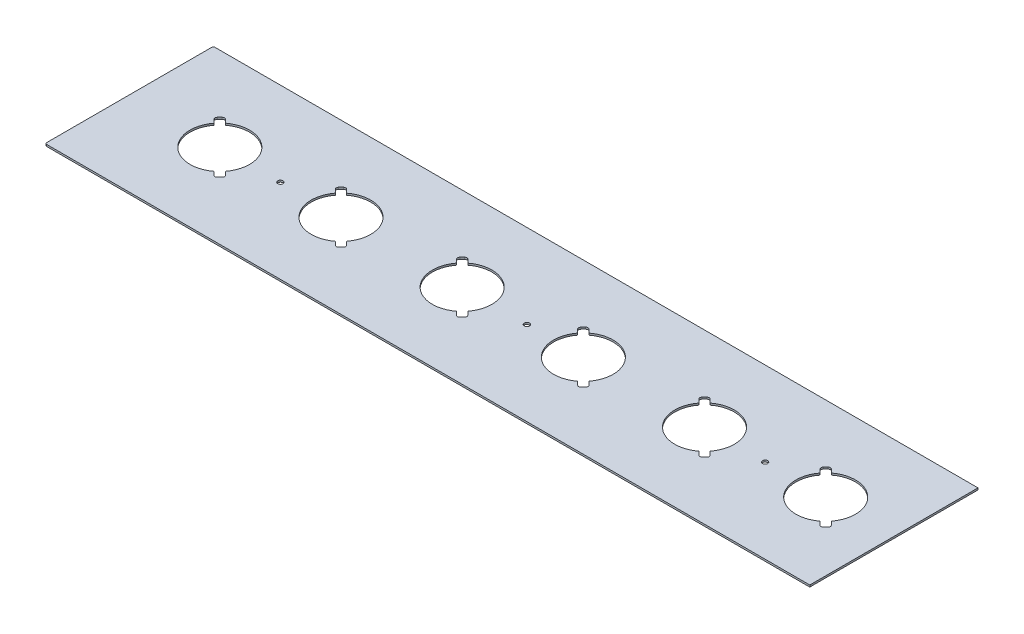
SolidWorks part; units mm, degrees
material "E-Glass Fiber"
ref_plane "Front" through (0, 0, 0) normal (0, 0, 1) x (1, 0, 0)
ref_plane "Top" through (0, 0, 0) normal (0, 1, 0) x (1, 0, 0)
ref_plane "Right" through (0, 0, 0) normal (1, 0, 0) x (0, 0, -1)
sketch "Sketch2" plane through (0, 0, 0) normal (0, 1, 0) x (1, 0, 0)
  line L1 (-317.5, 69.85) -> (317.5, 69.85)
  line L2 (-317.5, 69.85) -> (-317.5, -69.85)
  line L3 (-317.5, -69.85) -> (317.5, -69.85)
  line L5 (317.5, 69.85) -> (317.5, -69.85)
  line L6 (-317.5, 69.85) -> (317.5, -69.85) construction
  line L13 (180.1482, -15.1494) -> (182.7999, -17.8011) construction
  line L14 (182.7999, -20.6295) -> (180.8907, -22.5387) construction
  line L18 (178.0623, -22.5387) -> (175.4106, -19.887) construction
  line L19 (142.4601, 22.5387) -> (145.1118, 19.887) construction
  line L20 (140.3742, 15.1494) -> (137.7225, 17.8011) construction
  line L24 (137.7225, 20.6295) -> (139.6317, 22.5387) construction
  line L25 (179.9443, -14.9455) -> (182.7999, -17.8011)
  line L30 (182.7999, -20.6295) -> (180.8907, -22.5387)
  line L31 (178.0623, -22.5387) -> (175.2067, -19.6831)
  line L32 (142.4601, 22.5387) -> (145.3157, 19.6831)
  line L36 (140.5781, 14.9455) -> (137.7225, 17.8011)
  line L37 (137.7225, 20.6295) -> (139.6317, 22.5387)
  line L38 (39.7394, 15.1494) -> (37.0877, 17.8011) construction
  line L42 (243.0949, 22.5387) -> (245.7466, 19.887) construction
  line L43 (238.3573, 20.6295) -> (240.2665, 22.5387) construction
  line L44 (241.009, 15.1494) -> (238.3573, 17.8011) construction
  line L45 (243.0949, 22.5387) -> (245.9505, 19.6831)
  line L46 (238.3573, 20.6295) -> (240.2665, 22.5387)
  line L47 (241.2129, 14.9455) -> (238.3573, 17.8011)
  line L48 (280.783, -15.1494) -> (283.4347, -17.8011) construction
  line L49 (283.4347, -20.6295) -> (281.5255, -22.5387) construction
  line L50 (278.6971, -22.5387) -> (276.0454, -19.887) construction
  line L51 (280.5791, -14.9455) -> (283.4347, -17.8011)
  line L52 (283.4347, -20.6295) -> (281.5255, -22.5387)
  line L53 (278.6971, -22.5387) -> (275.8415, -19.6831)
  line L78 (37.0877, 20.6295) -> (38.9969, 22.5387) construction
  line L79 (41.8253, 22.5387) -> (44.477, 19.887) construction
  line L80 (79.5134, -15.1494) -> (82.1651, -17.8011) construction
  line L81 (82.1651, -20.6295) -> (80.2559, -22.5387) construction
  line L82 (77.4275, -22.5387) -> (74.7758, -19.887) construction
  line L83 (39.9433, 14.9455) -> (37.0877, 17.8011)
  line L84 (37.0877, 20.6295) -> (38.9969, 22.5387)
  line L85 (41.8253, 22.5387) -> (44.6809, 19.6831)
  line L86 (79.3095, -14.9455) -> (82.1651, -17.8011)
  line L87 (82.1651, -20.6295) -> (80.2559, -22.5387)
  line L88 (77.4275, -22.5387) -> (74.5719, -19.6831)
  line L89 (-60.8954, 15.1494) -> (-63.5471, 17.8011) construction
  line L90 (-63.5471, 20.6295) -> (-61.6379, 22.5387) construction
  line L91 (-58.8095, 22.5387) -> (-56.1578, 19.887) construction
  line L92 (-21.1214, -15.1494) -> (-18.4697, -17.8011) construction
  line L93 (-18.4697, -20.6295) -> (-20.3789, -22.5387) construction
  line L94 (-23.2073, -22.5387) -> (-25.859, -19.887) construction
  line L95 (-60.6915, 14.9455) -> (-63.5471, 17.8011)
  line L96 (-63.5471, 20.6295) -> (-61.6379, 22.5387)
  line L97 (-58.8095, 22.5387) -> (-55.9539, 19.6831)
  line L98 (-21.3253, -14.9455) -> (-18.4697, -17.8011)
  line L99 (-18.4697, -20.6295) -> (-20.3789, -22.5387)
  line L100 (-23.2073, -22.5387) -> (-26.0629, -19.6831)
  line L101 (-161.5302, 15.1494) -> (-164.1819, 17.8011) construction
  line L102 (-164.1819, 20.6295) -> (-162.2727, 22.5387) construction
  line L103 (-159.4443, 22.5387) -> (-156.7926, 19.887) construction
  line L104 (-121.7562, -15.1494) -> (-119.1045, -17.8011) construction
  line L105 (-119.1045, -20.6295) -> (-121.0137, -22.5387) construction
  line L106 (-123.8421, -22.5387) -> (-126.4938, -19.887) construction
  line L107 (-161.3263, 14.9455) -> (-164.1819, 17.8011)
  line L108 (-164.1819, 20.6295) -> (-162.2727, 22.5387)
  line L109 (-159.4443, 22.5387) -> (-156.5887, 19.6831)
  line L110 (-121.9601, -14.9455) -> (-119.1045, -17.8011)
  line L111 (-119.1045, -20.6295) -> (-121.0137, -22.5387)
  line L112 (-123.8421, -22.5387) -> (-126.6977, -19.6831)
  line L113 (-222.391, -15.1494) -> (-219.7393, -17.8011) construction
  line L114 (-219.7393, -20.6295) -> (-221.6485, -22.5387) construction
  line L115 (-224.4769, -22.5387) -> (-227.1286, -19.887) construction
  line L116 (-260.0791, 22.5387) -> (-257.4274, 19.887) construction
  line L117 (-264.8167, 20.6295) -> (-262.9075, 22.5387) construction
  line L118 (-262.165, 15.1494) -> (-264.8167, 17.8011) construction
  line L119 (-222.5949, -14.9455) -> (-219.7393, -17.8011)
  line L120 (-219.7393, -20.6295) -> (-221.6485, -22.5387)
  line L121 (-224.4769, -22.5387) -> (-227.3325, -19.6831)
  line L122 (-260.0791, 22.5387) -> (-257.2235, 19.6831)
  line L123 (-264.8167, 20.6295) -> (-262.9075, 22.5387)
  line L124 (-261.9611, 14.9455) -> (-264.8167, 17.8011)
  arc A16 (182.7999, -20.6295) -> (182.7999, -17.8011) centre (181.3857, -19.2153) ccw construction
  arc A20 (178.0623, -22.5387) -> (180.8907, -22.5387) centre (179.4765, -21.1245) ccw construction
  arc A24 (142.4601, 22.5387) -> (139.6317, 22.5387) centre (141.0459, 21.1245) ccw construction
  arc A28 (137.7225, 20.6295) -> (137.7225, 17.8011) centre (139.1367, 19.2153) ccw construction
  arc A45 (182.7999, -20.6295) -> (182.7999, -17.8011) centre (181.3857, -19.2153) ccw
  arc A46 (178.0623, -22.5387) -> (180.8907, -22.5387) centre (179.4765, -21.1245) ccw
  arc A47 (241.2129, 14.9455) -> (275.8415, -19.6831) centre (260.896, 0) ccw
  arc A48 (243.0949, 22.5387) -> (240.2665, 22.5387) centre (241.6807, 21.1245) ccw construction
  arc A49 (238.3573, 20.6295) -> (238.3573, 17.8011) centre (239.7715, 19.2153) ccw construction
  arc A50 (243.0949, 22.5387) -> (240.2665, 22.5387) centre (241.6807, 21.1245) ccw
  arc A51 (238.3573, 20.6295) -> (238.3573, 17.8011) centre (239.7715, 19.2153) ccw
  arc A52 (283.4347, -20.6295) -> (283.4347, -17.8011) centre (282.0205, -19.2153) ccw construction
  arc A53 (278.6971, -22.5387) -> (281.5255, -22.5387) centre (280.1113, -21.1245) ccw construction
  arc A54 (283.4347, -20.6295) -> (283.4347, -17.8011) centre (282.0205, -19.2153) ccw
  arc A55 (278.6971, -22.5387) -> (281.5255, -22.5387) centre (280.1113, -21.1245) ccw
  arc A56 (280.5791, -14.9455) -> (245.9505, 19.6831) centre (260.896, 0) ccw
  arc A79 (142.4601, 22.5387) -> (139.6317, 22.5387) centre (141.0459, 21.1245) ccw
  arc A80 (137.7225, 20.6295) -> (137.7225, 17.8011) centre (139.1367, 19.2153) ccw
  arc A81 (179.9443, -14.9455) -> (145.3157, 19.6831) centre (160.2612, 0) ccw
  arc A82 (140.5781, 14.9455) -> (175.2067, -19.6831) centre (160.2612, 0) ccw
  arc A83 (37.0877, 20.6295) -> (37.0877, 17.8011) centre (38.5019, 19.2153) ccw construction
  arc A84 (41.8253, 22.5387) -> (38.9969, 22.5387) centre (40.4111, 21.1245) ccw construction
  arc A85 (82.1651, -20.6295) -> (82.1651, -17.8011) centre (80.7509, -19.2153) ccw construction
  arc A86 (77.4275, -22.5387) -> (80.2559, -22.5387) centre (78.8417, -21.1245) ccw construction
  arc A87 (37.0877, 20.6295) -> (37.0877, 17.8011) centre (38.5019, 19.2153) ccw
  arc A88 (41.8253, 22.5387) -> (38.9969, 22.5387) centre (40.4111, 21.1245) ccw
  arc A89 (82.1651, -20.6295) -> (82.1651, -17.8011) centre (80.7509, -19.2153) ccw
  arc A90 (77.4275, -22.5387) -> (80.2559, -22.5387) centre (78.8417, -21.1245) ccw
  arc A91 (-63.5471, 20.6295) -> (-63.5471, 17.8011) centre (-62.1329, 19.2153) ccw construction
  arc A92 (-58.8095, 22.5387) -> (-61.6379, 22.5387) centre (-60.2237, 21.1245) ccw construction
  arc A93 (-18.4697, -20.6295) -> (-18.4697, -17.8011) centre (-19.8839, -19.2153) ccw construction
  arc A94 (-23.2073, -22.5387) -> (-20.3789, -22.5387) centre (-21.7931, -21.1245) ccw construction
  arc A95 (-63.5471, 20.6295) -> (-63.5471, 17.8011) centre (-62.1329, 19.2153) ccw
  arc A96 (-58.8095, 22.5387) -> (-61.6379, 22.5387) centre (-60.2237, 21.1245) ccw
  arc A97 (-18.4697, -20.6295) -> (-18.4697, -17.8011) centre (-19.8839, -19.2153) ccw
  arc A98 (-23.2073, -22.5387) -> (-20.3789, -22.5387) centre (-21.7931, -21.1245) ccw
  arc A99 (-164.1819, 20.6295) -> (-164.1819, 17.8011) centre (-162.7677, 19.2153) ccw construction
  arc A100 (-159.4443, 22.5387) -> (-162.2727, 22.5387) centre (-160.8585, 21.1245) ccw construction
  arc A101 (-119.1045, -20.6295) -> (-119.1045, -17.8011) centre (-120.5187, -19.2153) ccw construction
  arc A102 (-123.8421, -22.5387) -> (-121.0137, -22.5387) centre (-122.4279, -21.1245) ccw construction
  arc A103 (-164.1819, 20.6295) -> (-164.1819, 17.8011) centre (-162.7677, 19.2153) ccw
  arc A104 (-159.4443, 22.5387) -> (-162.2727, 22.5387) centre (-160.8585, 21.1245) ccw
  arc A105 (-119.1045, -20.6295) -> (-119.1045, -17.8011) centre (-120.5187, -19.2153) ccw
  arc A106 (-123.8421, -22.5387) -> (-121.0137, -22.5387) centre (-122.4279, -21.1245) ccw
  arc A107 (-219.7393, -20.6295) -> (-219.7393, -17.8011) centre (-221.1535, -19.2153) ccw construction
  arc A108 (-224.4769, -22.5387) -> (-221.6485, -22.5387) centre (-223.0627, -21.1245) ccw construction
  arc A109 (-260.0791, 22.5387) -> (-262.9075, 22.5387) centre (-261.4933, 21.1245) ccw construction
  arc A110 (-264.8167, 20.6295) -> (-264.8167, 17.8011) centre (-263.4025, 19.2153) ccw construction
  arc A111 (-219.7393, -20.6295) -> (-219.7393, -17.8011) centre (-221.1535, -19.2153) ccw
  arc A112 (-224.4769, -22.5387) -> (-221.6485, -22.5387) centre (-223.0627, -21.1245) ccw
  arc A113 (-260.0791, 22.5387) -> (-262.9075, 22.5387) centre (-261.4933, 21.1245) ccw
  arc A114 (-264.8167, 20.6295) -> (-264.8167, 17.8011) centre (-263.4025, 19.2153) ccw
  arc A115 (79.3095, -14.9455) -> (44.6809, 19.6831) centre (59.6264, 0) ccw
  arc A116 (-21.3253, -14.9455) -> (-55.9539, 19.6831) centre (-41.0084, 0) ccw
  arc A117 (-121.9601, -14.9455) -> (-156.5887, 19.6831) centre (-141.6432, 0) ccw
  arc A118 (-222.5949, -14.9455) -> (-257.2235, 19.6831) centre (-242.278, 0) ccw
  arc A119 (-261.9611, 14.9455) -> (-227.3325, -19.6831) centre (-242.278, 0) ccw
  arc A120 (-161.3263, 14.9455) -> (-126.6977, -19.6831) centre (-141.6432, 0) ccw
  arc A121 (-60.6915, 14.9455) -> (-26.0629, -19.6831) centre (-41.0084, 0) ccw
  arc A122 (39.9433, 14.9455) -> (74.5719, -19.6831) centre (59.6264, 0) ccw
  point P0 (0, 0)
  dimension "D3" = 24.7142
  dimension "D1" = 635
  dimension "D2" = 139.7
extrude "Boss-Extrude1" add sketch "Sketch2" along normal blind 1.524
sketch "Sketch3" [suppressed] plane through (0, 1.524, 0) normal (0, 1, 0) x (1, 0, 0)
  line L42 (-317.5, -69.85) -> (-292.1, -69.85) construction
  line L43 (285.896, 0) -> (287.166, 0)
  line L44 (-317.5, 69.85) -> (-317.5, -69.85) construction
  line L45 (-317.5, 49.8475) -> (-317.5, 69.85) construction
  line L46 (260.896, -26.27) -> (260.896, 26.27) construction
  line L47 (-292.1, -69.85) -> (-292.1, 69.85)
  line L48 (-292.1, 49.8475) -> (-317.5, 49.8475)
  line L49 (234.626, 26.27) -> (287.166, 26.27) construction
  line L50 (-292.1, -49.8475) -> (-317.5, -49.8475)
  line L51 (-317.5, -49.8475) -> (-317.5, -69.85) construction
  line L52 (287.166, 0) -> (287.166, -26.27)
  line L53 (287.166, 0) -> (234.626, 0) construction
  line L54 (234.626, -26.27) -> (234.626, 26.27) construction
  line L55 (260.896, 26.27) -> (234.626, 26.27)
  line L57 (234.626, 26.27) -> (234.626, 0)
  line L58 (234.626, 0) -> (235.896, 0)
  line L59 (260.896, 26.27) -> (260.896, 25)
  line L61 (287.166, -26.27) -> (260.896, -26.27)
  line L63 (260.896, -26.27) -> (260.896, -25)
  line L64 (160.261, -26.27) -> (160.261, 26.27) construction
  line L65 (133.991, 26.27) -> (186.531, 26.27) construction
  line L67 (186.531, -26.27) -> (133.991, -26.27) construction
  line L68 (186.531, 0) -> (133.991, 0) construction
  line L69 (133.991, -26.27) -> (133.991, 26.27) construction
  line L70 (160.261, 26.27) -> (133.991, 26.27)
  line L71 (133.991, 26.27) -> (133.991, 0)
  line L72 (133.991, 0) -> (135.261, 0)
  line L73 (160.261, 26.27) -> (160.261, 25)
  line L74 (185.261, 0) -> (186.531, 0)
  line L75 (186.531, 0) -> (186.531, -26.27)
  line L76 (186.531, -26.27) -> (160.261, -26.27)
  line L77 (160.261, -26.27) -> (160.261, -25)
  line L78 (59.626, -26.27) -> (59.626, 26.27) construction
  line L79 (33.356, 26.27) -> (85.896, 26.27) construction
  line L81 (85.896, -26.27) -> (33.356, -26.27) construction
  line L82 (85.896, 0) -> (33.356, 0) construction
  line L83 (33.356, -26.27) -> (33.356, 26.27) construction
  line L85 (59.626, 25) -> (59.626, 26.27)
  line L86 (59.626, 26.27) -> (33.356, 26.27)
  line L87 (33.356, 26.27) -> (33.356, 0)
  line L88 (33.356, 0) -> (34.626, 0)
  line L90 (84.626, 0) -> (85.896, 0)
  line L92 (85.896, 0) -> (85.896, -26.27)
  line L93 (85.896, -26.27) -> (59.626, -26.27)
  line L94 (59.626, -26.27) -> (59.626, -25)
  line L96 (-292.1, 49.5863) -> (-292.1, 88.9) construction
  line L97 (317.5, 69.85) -> (-317.5, 69.85) construction
  line L98 (-317.5, -69.85) -> (317.5, -69.85) construction
  line L99 (317.5, 69.85) -> (-317.5, 69.85) construction
  arc A24 (241.009, 15.1494) -> (276.0454, -19.887) centre (260.896, 0) ccw construction
  arc A25 (280.783, -15.1494) -> (245.7466, 19.887) centre (260.896, 0) ccw construction
  arc A26 (140.374, 15.1494) -> (175.4104, -19.887) centre (160.261, 0) ccw construction
  arc A27 (180.148, -15.1494) -> (145.1116, 19.887) centre (160.261, 0) ccw construction
  point P8 (260.896, 0)
  point P16 (160.261, 0)
  point P17 (260.896, 0)
  point P37 (160.261, 0)
  point P52 (59.626, 0)
  point P60 (59.626, 0)
  dimension "D1" = 20.0025
fillet "Fillet1" radius 1.27 2 edges at (-317.5, 0.762, 69.85) (-317.5, 0.762, -69.85)
hole_wizard "#8 Clearance Hole1" positions "Sketch4" profile "Sketch5" hole size "#8" standard "ANSI Inch" end condition through all
sketch "Sketch4" plane through (0, 1.524, 0) normal (0, 1, 0) x (1, 0, 0)
  point P0 (210.5786, 0)
  point P3 (12.7, 0)
  point P6 (-191.9606, 0)
sketch "Sketch5" plane through (210.5786, 1.524, 0) normal (1, 0, 0) x (0, 0, 1)
  line L0 (0, 0) -> (0, 1.524)
  line L1 (0, 1.524) -> (2.1526, 1.524)
  line L2 (2.1526, 1.524) -> (2.1526, 0)
  line L5 (2.1526, 0) -> (0, 0)
  line L11 (0, -6.35) -> (0, 107.95) construction
  dimension "Thru Hole Dia." = 4.3053
  dimension "Thru Hole Depth" = 1.524
